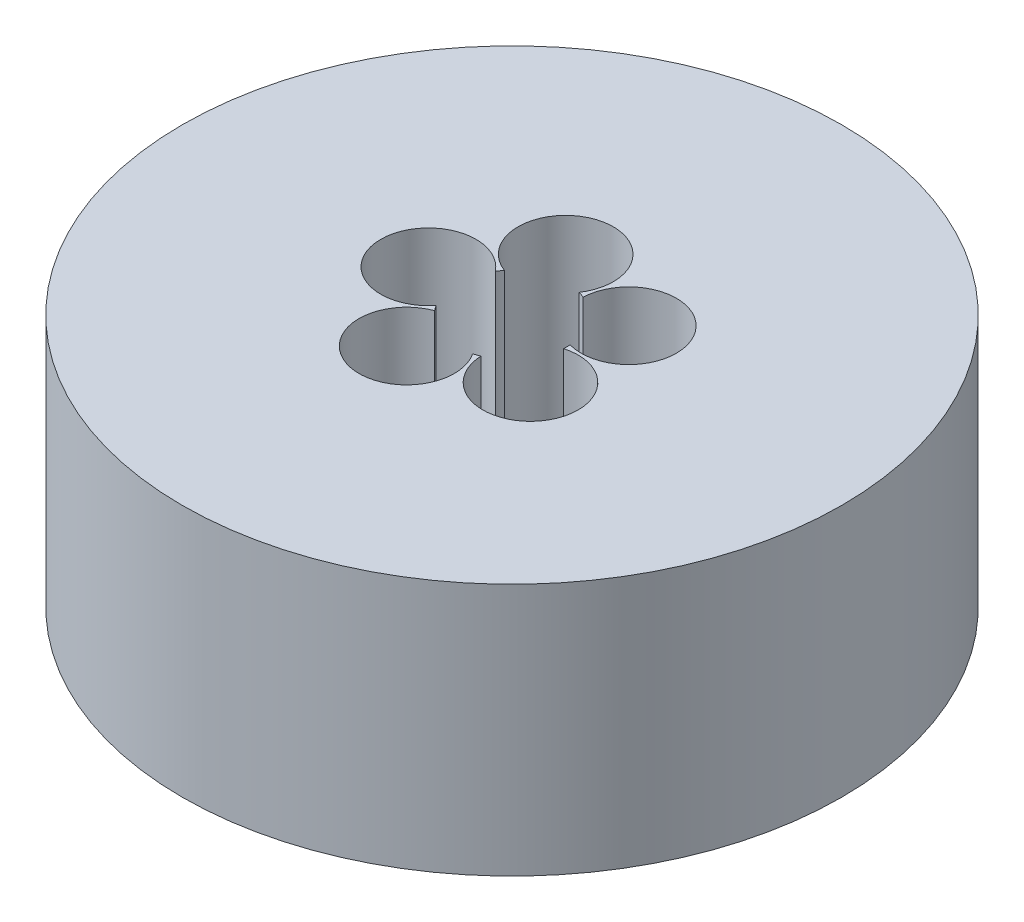
SolidWorks part; units mm, degrees
ref_plane "Front Plane" through (0, 0, 0) normal (0, 0, 1) x (1, 0, 0)
ref_plane "Top Plane" through (0, 0, 0) normal (0, 1, 0) x (1, 0, 0)
ref_plane "Right Plane" through (0, 0, 0) normal (1, 0, 0) x (0, 0, -1)
sketch "Sketch1" plane through (0, 0, 0) normal (0, 1, 0) x (1, 0, 0)
  circle A0 centre (0, 0) radius 30
  dimension "FLANGE_OD" = 60
extrude "Boss-Extrude1" add sketch "Sketch1" along normal blind 23
sketch "Sketch2" plane through (0, 0, 0) normal (0, 1, 0) x (1, 0, 0)
  circle A0 centre (0, 0) radius 5
  dimension "BORE_D" = 10
extrude "Cut-Extrude1" cut sketch "Sketch2" along normal through all
sketch "Sketch3" plane through (0, 23, 0) normal (0, 1, 0) x (1, 0, 0)
  circle A0 centre (0, 0) radius 7.6067 construction
  circle A1 centre (-7.6067, 0) radius 4.3349
  dimension "BOLT_D" = 8.6699
  dimension "BOLT_PCD" = 15.2134
extrude "Cut-Extrude2" cut sketch "Sketch3" against normal blind 20.0346
pattern_circular "CirPattern1" count 5 over 360 about axis through (0, 0, 0) along (0, 1, 0) of "Cut-Extrude2"
